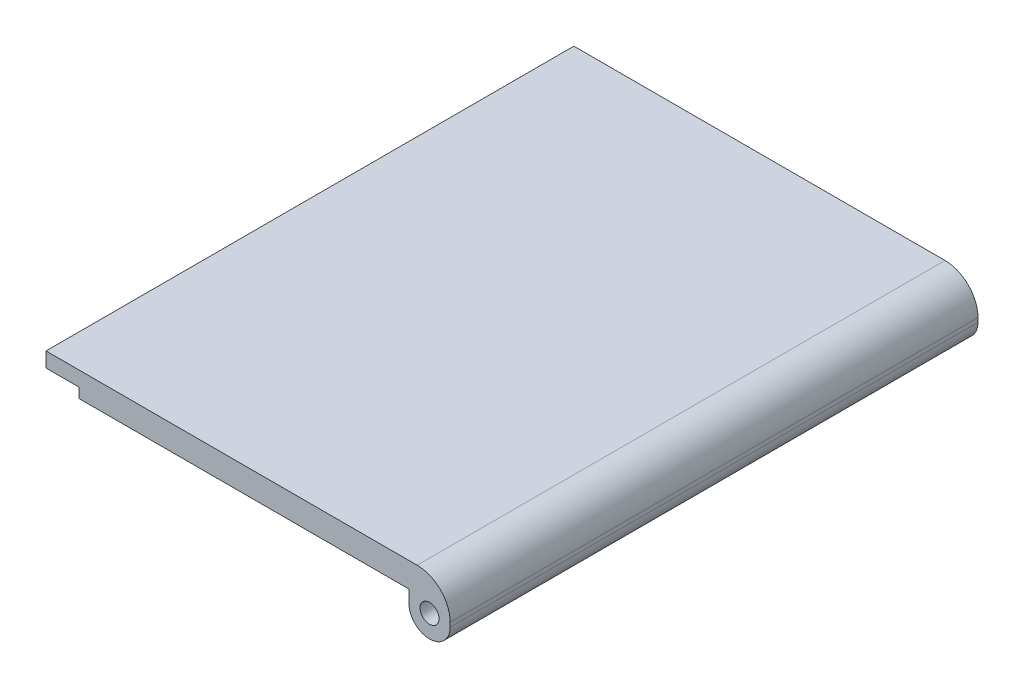
SolidWorks part; units mm, degrees
ref_plane "Front" through (0, 0, 0) normal (0, 0, 1) x (1, 0, 0)
ref_plane "Top" through (0, 0, 0) normal (0, 1, 0) x (1, 0, 0)
ref_plane "Right" through (0, 0, 0) normal (1, 0, 0) x (0, 0, -1)
sketch "草图1" plane through (0, 0, 0) normal (0, 1, 0) x (1, 0, 0)
  line L1 (-24.5, 32) -> (24.5, 32)
  line L2 (-24.5, 32) -> (-24.5, -32)
  line L3 (-24.5, -32) -> (24.5, -32)
  line L4 (24.5, 32) -> (24.5, -32)
  line L5 (-24.5, 32) -> (24.5, -32) construction
  line L6 (-24.5, -32) -> (24.5, 32) construction
  point P0 (0, 0)
  dimension "D1" = 49
  dimension "D2" = 64
extrude "凸台-拉伸1" add sketch "草图1" along normal blind 3
sketch "草图2" plane through (0, 0, 0) normal (0, -1, 0) x (-1, 0, 0)
  line L0 (-24.5, 32) -> (24.5, 32) construction
  line L1 (-24.5, -32) -> (-19.5, -32)
  line L2 (-24.5, -32) -> (-24.5, 32)
  line L3 (-24.5, 32) -> (-19.5, 32)
  line L4 (-19.5, -32) -> (-19.5, 32)
  dimension "D1" = 5
extrude "凸台-拉伸2" add sketch "草图2" along normal blind 4
sketch "草图3" plane through (0, 0, -32) normal (0, 0, -1) x (-1, 0, 0)
  line L2 (-24.5, 3) -> (-24.5, -4) construction
  line L3 (-24.5, 3) -> (24.5, 3) construction
  circle A0 centre (-22, -1.3) radius 1.15
  dimension "D1" = 2.5
  dimension "D3" = 2.3
  dimension "D2" = 4.3
extrude "切除-拉伸2" cut sketch "草图3" against normal through all
fillet "圆角1" radius 2.5 2 edges at (24.5, -4, 0) (19.5, -4, 0)
fillet "圆角2" radius 4 1 edges at (24.5, 3, 0)
sketch "草图4" plane through (0, 0, 0) normal (0, -1, 0) x (-1, 0, 0)
  line L0 (24.5, 32) -> (24.5, -32) construction
  line L1 (24.5, -32) -> (-19.5, -32) construction
  line L2 (31.021, 0) -> (7.3044, 0) construction
  line L3 (24.5, -28) -> (24.5, -32)
  line L4 (24.5, -32) -> (20.5, -32)
  line L5 (24.5, 28) -> (24.5, 32)
  line L6 (24.5, 32) -> (20.5, 32)
  arc A0 (24.5, -28) -> (20.5, -32) centre (24.5, -32) ccw
  arc A1 (24.5, 28) -> (20.5, 32) centre (24.5, 32) cw
  dimension "D1" = 4
extrude "切除-拉伸3" cut sketch "草图4" against normal blind 1.2
